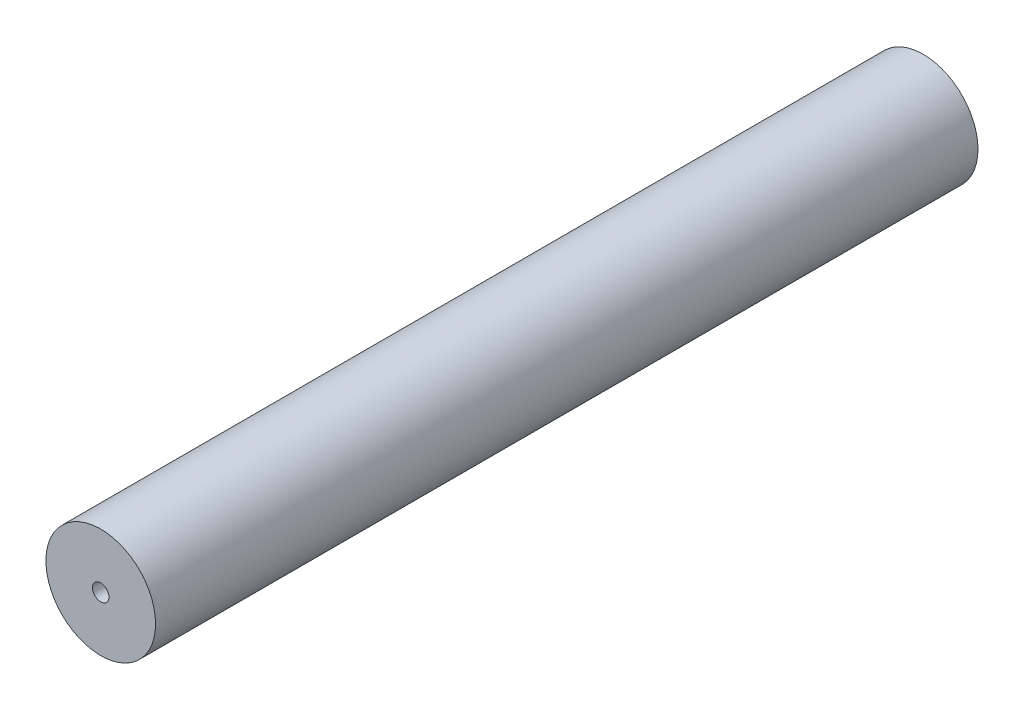
SolidWorks part; units mm, degrees
ref_plane "Front Plane" through (0, 0, 0) normal (0, 0, 1) x (1, 0, 0)
ref_plane "Top Plane" through (0, 0, 0) normal (0, 1, 0) x (1, 0, 0)
ref_plane "Right Plane" through (0, 0, 0) normal (1, 0, 0) x (0, 0, -1)
sketch "Sketch1" plane through (0, 0, 0) normal (0, 0, 1) x (1, 0, 0)
  circle A0 centre (0, 0) radius 20
  dimension "D1" = 40
extrude "Boss-Extrude1" add sketch "Sketch1" along normal blind 300
sketch "Sketch3" plane through (0, 0, 300) normal (0, 0, 1) x (1, 0, 0)
  circle A5 centre (0, 0) radius 3
extrude "Cut-Extrude1" cut sketch "Sketch3" against normal blind 20
